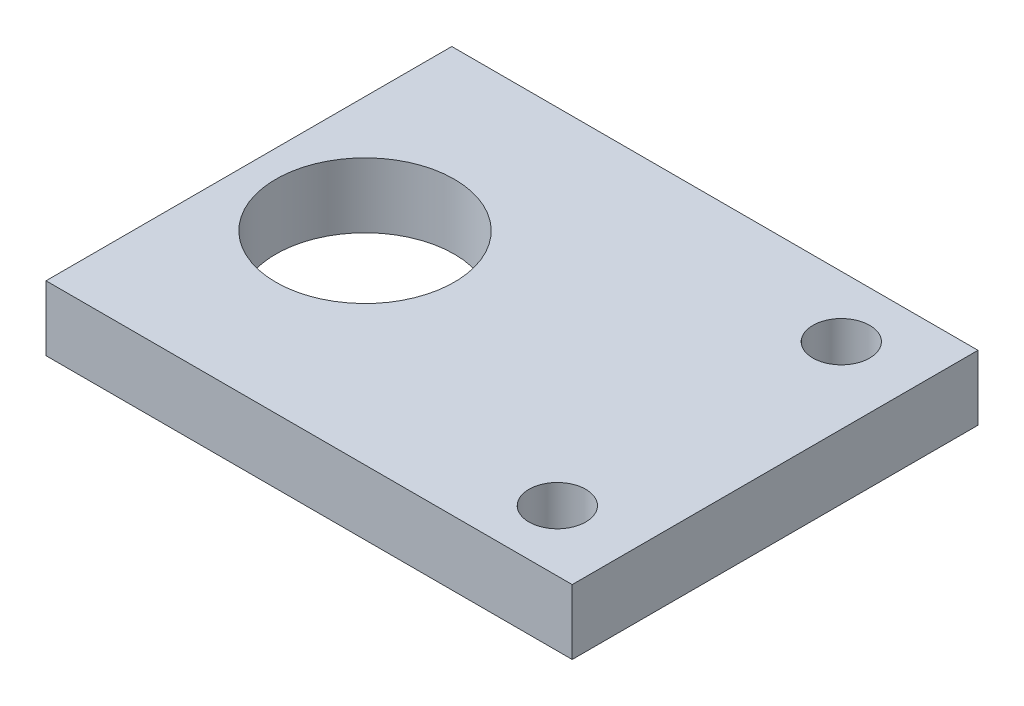
SolidWorks part; units mm, degrees
ref_plane "Front Plane" through (0, 0, 0) normal (0, 0, 1) x (1, 0, 0)
ref_plane "Top Plane" through (0, 0, 0) normal (0, 1, 0) x (1, 0, 0)
ref_plane "Right Plane" through (0, 0, 0) normal (1, 0, 0) x (0, 0, -1)
sketch "Sketch1" plane through (0, 0, 0) normal (0, 1, 0) x (1, 0, 0)
  line L0 (0, 61.7725) -> (0, -64.7928) construction
  line L3 (-26.0804, -8) -> (-26.0804, 8)
  line L6 (-9.001, 12.5039) -> (6.3491, 12.5039)
  line L7 (6.3491, 12.5039) -> (6.3491, 8)
  line L8 (-4.6226, 0) -> (9.2617, 0) construction
  line L9 (6.3491, -12.5039) -> (6.3491, -8)
  line L10 (-9.001, -12.5039) -> (6.3491, -12.5039)
  line L12 (6.3491, 8) -> (6.3491, -8)
  line L13 (-26.0804, 8) -> (-26.0804, 12.5039)
  line L14 (-26.0804, 12.5039) -> (-9.001, 12.5039)
  line L15 (-26.0804, -12.5039) -> (-9.001, -12.5039)
  line L16 (-26.0804, -8) -> (-26.0804, -12.5039)
  circle A0 centre (-18.922, 0) radius 9.5
  circle A1 centre (1.678, 8.75) radius 1.75
  circle A2 centre (1.678, -8.75) radius 1.75
  circle A3 centre (-18.922, 0) radius 5.5
  point P3 (0, 0)
  dimension "D1" = 11
  dimension "D2" = 20.6
  dimension "D3" = 19
  dimension "D4" = 8.75
extrude "Boss-Extrude1" add sketch "Sketch1" along normal blind 4 contours L3 L16 L15 L10 L9 L12 L7 L6 L14 L13 A0 A1 A2 | A0 A3 region at (-6.0764, 0, 0) region at (-25.8278, 0, 0)
